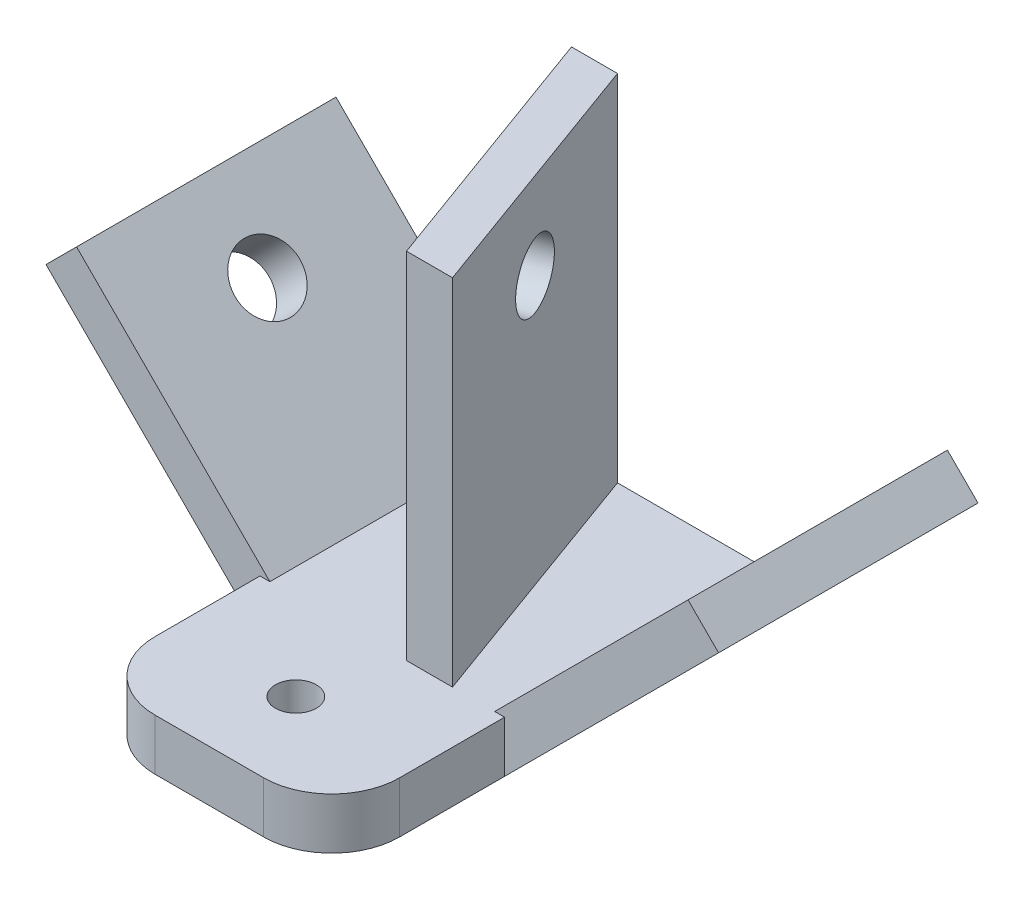
SolidWorks part; units mm, degrees
ref_plane "Front Plane" through (0, 0, 0) normal (0, 0, 1) x (1, 0, 0)
ref_plane "Top Plane" through (0, 0, 0) normal (0, 1, 0) x (1, 0, 0)
ref_plane "Right Plane" through (0, 0, 0) normal (1, 0, 0) x (0, 0, -1)
sketch "Sketch1" plane through (0, 0, 0) normal (0, 0, 1) x (1, 0, 0)
  line L0 (-44.9013, 44.9013) -> (0, 0)
  line L1 (0, 0) -> (44.9013, 44.9013)
  line L2 (44.9013, 44.9013) -> (49.3914, 40.4112)
  line L3 (49.3914, 40.4112) -> (0, -8.9803)
  line L4 (0, -8.9803) -> (-49.3914, 40.4112)
  line L5 (-49.3914, 40.4112) -> (-44.9013, 44.9013)
  line L6 (0, -8.9803) -> (0, 0) construction
  dimension "D1" = 6.35
  dimension "D2" = 63.5
extrude "Boss-Extrude1" add sketch "Sketch1" along normal mid plane 38.1
sketch "Sketch2" plane through (0, 0, 0) normal (0, 1, 0) x (1, 0, 0)
  line L0 (-10.3124, 19.05) -> (-3.5549, 19.05)
  line L1 (0, 19.05) -> (-44.9013, 19.05) construction
  line L2 (-3.5549, 19.05) -> (10.3124, -19.05)
  line L3 (44.9013, -19.05) -> (0, -19.05) construction
  line L4 (10.3124, -19.05) -> (3.5549, -19.05)
  line L5 (3.5549, -19.05) -> (-10.3124, 19.05)
  line L6 (-6.9336, 19.05) -> (6.9336, -19.05) construction
  line L7 (0, -19.05) -> (-44.9013, -19.05) construction
  point P10 (0, 0)
  dimension "D1" = 6.35
  dimension "D2" = 70
extrude "Boss-Extrude2" add sketch "Sketch2" against normal up to body and the other way blind 63.5 from offset 5.08 separate body
sketch "Sketch3" plane through (-4.4901, -4.4901, 0) normal (-0.7071, -0.7071, 0) x (0, 0, 1)
  line L0 (19.05, 63.5) -> (-19.05, 63.5) construction
  circle A0 centre (0, 50.8) radius 4.7625
  point P4 (0, 63.5)
  dimension "D1" = 9.525
  dimension "D2" = 12.7
extrude "Cut-Extrude1" cut sketch "Sketch3" against normal up to next
mirror "Mirror1" about plane through (0, 0, 0) normal (1, 0, 0) of "Cut-Extrude1"
sketch "Sketch4" plane through (2.9835, 0, -1.0859) normal (0.9397, 0, -0.342) x (-0.342, 0, -0.9397)
  line L0 (-21.4282, 68.58) -> (19.117, 68.58) construction
  circle A0 centre (-1.1556, 55.88) radius 4.7625
  point P4 (-1.1556, 68.58)
  dimension "D2" = 9.525
  dimension "D1" = 12.7
extrude "Cut-Extrude2" cut sketch "Sketch4" against normal up to next
sketch "Sketch5" plane through (0, 0, 19.05) normal (0, 0, 1) x (1, 0, 0)
  line L0 (-16.51, 16.51) -> (16.51, 16.51)
  line L1 (0, 0) -> (-44.9013, 44.9013) construction
  line L2 (44.9013, 44.9013) -> (10.3124, 10.3124) construction
  line L3 (16.51, 16.51) -> (0, 0)
  line L4 (0, 0) -> (-16.51, 16.51)
  dimension "D1" = 16.51
extrude "Boss-Extrude3" add sketch "Sketch5" against normal up to surface (38.1 mm away) up to face at (-2.7735, 31.2672, -19.05)
chamfer "Chamfer1" distance 25.4 angle 45 1 edges at (0, -8.9803, 0)
sketch "Sketch6" plane through (0, 8.9803, 0) normal (0, -1, 0) x (1, 0, 0)
  line L1 (-17.9605, 19.05) -> (17.9605, 19.05)
  line L2 (-17.9605, 19.05) -> (-17.9605, 44.45)
  line L3 (-17.9605, 44.45) -> (17.9605, 44.45)
  line L4 (17.9605, 19.05) -> (17.9605, 44.45)
  line L5 (-17.9605, 19.05) -> (17.9605, 44.45) construction
  line L6 (-17.9605, 44.45) -> (17.9605, 19.05) construction
  point P4 (0, 31.75)
  dimension "D1" = 25.4
extrude "Boss-Extrude4" add sketch "Sketch6" against normal up to surface (7.5297 mm away) up to face at (-9.9444, 16.51, 0)
sketch "Sketch7" plane through (0, 16.51, 0) normal (0, 1, 0) x (1, 0, 0)
  line L0 (-17.9605, -44.45) -> (-17.9605, -19.05) construction
  line L1 (17.9605, -44.45) -> (-17.9605, -44.45) construction
  circle A0 centre (0, -31.75) radius 3
  point P4 (-17.9605, -31.75)
  point P7 (0, -44.45)
  dimension "D1" = 6
extrude "Cut-Extrude3" cut sketch "Sketch7" against normal through all
fillet "Fillet1" radius 10 2 edges at (17.9605, 12.7451, 44.45) (-17.9605, 12.7451, 44.45)
